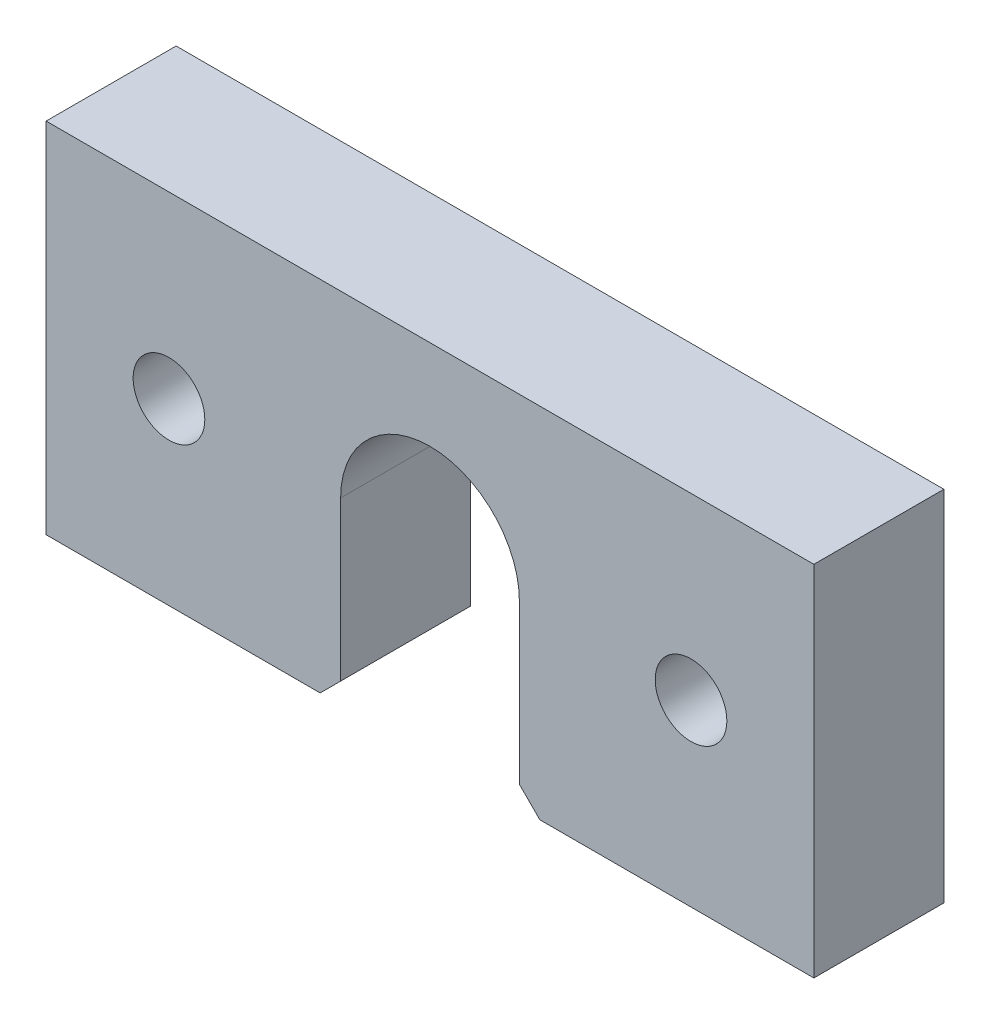
SolidWorks part; units mm, degrees
ref_plane "Front Plane" through (0, 0, 0) normal (0, 0, 1) x (1, 0, 0)
ref_plane "Top Plane" through (0, 0, 0) normal (0, 1, 0) x (1, 0, 0)
ref_plane "Right Plane" through (0, 0, 0) normal (1, 0, 0) x (0, 0, -1)
sketch "Sketch1" plane through (0, 0, 0) normal (0, 0, 1) x (1, 0, 0)
  line L1 (37.5, -17.5) -> (-37.5, -17.5)
  line L2 (37.5, -17.5) -> (37.5, 17.5)
  line L3 (37.5, 17.5) -> (-37.5, 17.5)
  line L4 (-37.5, -17.5) -> (-37.5, 17.5)
  line L5 (37.5, -17.5) -> (-37.5, 17.5) construction
  line L6 (37.5, 17.5) -> (-37.5, -17.5) construction
  point P0 (0, 0)
  dimension "D1" = 75
  dimension "D2" = 35
extrude "Boss-Extrude1" add sketch "Sketch1" along normal blind 12.7
sketch "Sketch2" plane through (0, 0, 0) normal (0, 0, -1) x (-1, 0, 0)
  line L0 (-8.7312, 0) -> (-8.7312, -17.5)
  line L1 (37.5, -17.5) -> (-37.5, -17.5) construction
  line L2 (8.7312, 0) -> (8.7312, -17.5)
  line L3 (37.5, 17.5) -> (37.5, -17.5) construction
  line L4 (-8.7312, -17.5) -> (8.7312, -17.5)
  arc A0 (8.7312, 0) -> (-8.7312, 0) centre (0, 0) ccw
  dimension "D1" = 17.4625
  dimension "D3" = 8.7688
  dimension "D4" = 28.7688
  dimension "D2" = 0
extrude "Cut-Extrude1" cut sketch "Sketch2" against normal up to next
hole_wizard "M8x1.0 Tapped Hole1" positions "Sketch5" profile "Sketch4" tap size "M8x1.0" standard "ANSI Metric" end condition through all
sketch "Sketch5" plane through (0, 0, 12.7) normal (0, 0, 1) x (1, 0, 0)
  line L0 (0, 0) -> (0, 8.7312) construction
  arc A0 (8.7312, 0) -> (-8.7312, 0) centre (0, 0) ccw construction
  point P0 (-25.5, 0)
  point P2 (25.5, 0)
  dimension "D1" = 51
sketch "Sketch4" plane through (-25.5, 0, 12.7) normal (1, 0, 0) x (0, -1, 0)
  line L0 (0, 0) -> (0, 12.7)
  line L1 (0, 12.7) -> (3.5, 12.7)
  line L2 (3.5, 12.7) -> (3.5, 0)
  line L5 (3.5, 0) -> (0, 0)
  line L11 (0, -6.35) -> (0, 107.95) construction
  dimension "Thru Tap Drill Dia." = 7
  dimension "Thru Tap Drill Depth" = 12.7
cosmetic thread "Hole Thread1" parameters "D2"=8
cosmetic thread "Hole Thread2" parameters "D2"=8
chamfer "Chamfer1" distance 2 angle 45 2 edges at (8.7312, -17.5, 6.35) (-8.7312, -17.5, 6.35)
